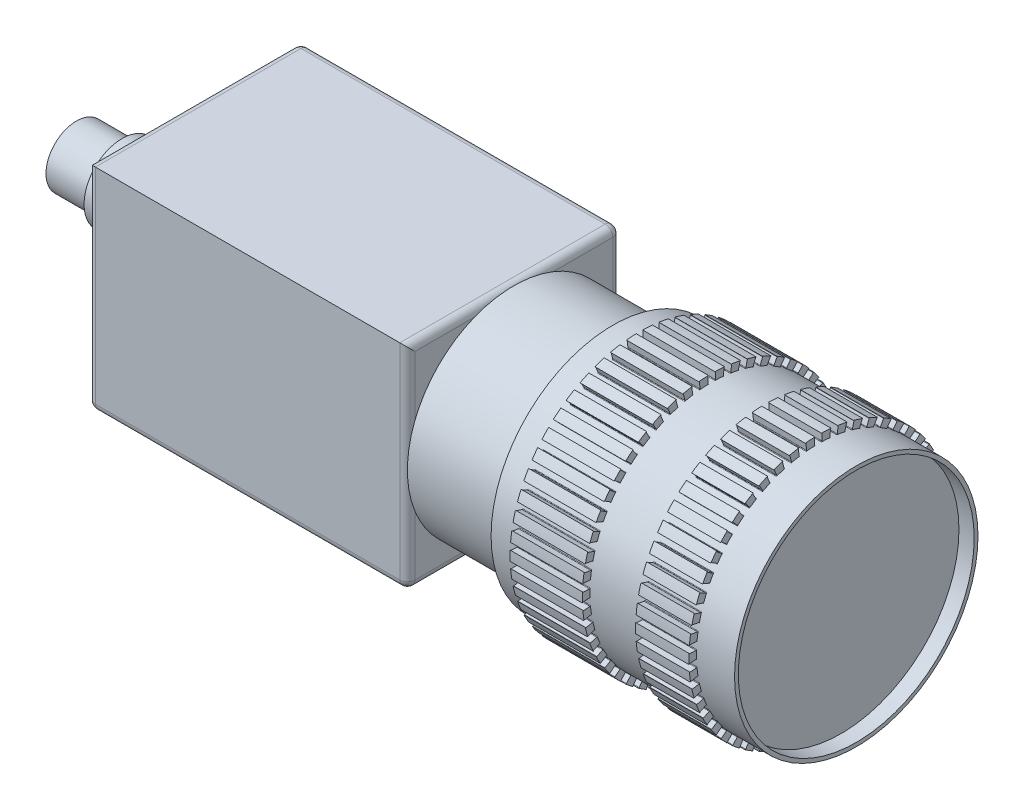
SolidWorks part; units mm, degrees
ref_plane "Front Plane" through (0, 0, 0) normal (0, 0, 1) x (1, 0, 0)
ref_plane "Top Plane" through (0, 0, 0) normal (0, 1, 0) x (1, 0, 0)
ref_plane "Right Plane" through (0, 0, 0) normal (1, 0, 0) x (0, 0, -1)
sketch "Sketch1" plane through (0, 0, 0) normal (0, 1, 0) x (1, 0, 0)
  line L1 (21, -14) -> (-21, -14)
  line L2 (21, -14) -> (21, 14)
  line L3 (21, 14) -> (-21, 14)
  line L4 (-21, -14) -> (-21, 14)
  line L5 (21, -14) -> (-21, 14) construction
  line L6 (21, 14) -> (-21, -14) construction
  point P0 (0, 0)
  dimension "D1" = 42
  dimension "D2" = 28
extrude "Boss-Extrude1" add sketch "Sketch1" along normal blind 28
fillet "Fillet1" radius 1 11 edges at (21, 14, 14) (21, 28, 0) (-21, 28, 0) (-21, 14, 14) (0, 0, 14) (21, 0, 0) (-21, 0, 0) (21, 14, -14) (0, 28, -14) (-21, 14, -14) (0, 0, -14)
sketch "Sketch2" plane through (21, 0, 0) normal (1, 0, 0) x (0, 0, -1)
  circle A0 centre (0, 14) radius 14
  dimension "D1" = 28
  dimension "D2" = 14
extrude "Boss-Extrude2" add sketch "Sketch2" along normal blind 13
sketch "Sketch3" plane through (34, 0, 0) normal (1, 0, 0) x (0, 0, -1)
  circle A0 centre (0, 14) radius 16
  circle A1 centre (0, 14) radius 14 construction
  dimension "D1" = 32
extrude "Boss-Extrude3" add sketch "Sketch3" along normal blind 3.5
sketch "Sketch4" plane through (37.5, 0, 0) normal (1, 0, 0) x (0, 0, -1)
  circle A0 centre (0, 14) radius 17
  circle A1 centre (0, 14) radius 16 construction
  dimension "D1" = 34
extrude "Boss-Extrude4" add sketch "Sketch4" along normal blind 9.5
sketch "Sketch5" plane through (47, 0, 0) normal (1, 0, 0) x (0, 0, -1)
  line L0 (-0.5, 30.9197) -> (-0.5, 30.0694)
  line L1 (1.6245, 30.8489) -> (1.518, 30.0053)
  line L2 (0.5, 30.0694) -> (0.5, 30.9197)
  line L3 (2.5101, 29.88) -> (2.6167, 30.7236)
  line L4 (3.7235, 30.5124) -> (3.512, 29.6889)
  line L5 (4.4806, 29.4402) -> (4.692, 30.2638)
  line L6 (5.7637, 29.9156) -> (5.4506, 29.125)
  line L7 (6.3804, 28.7569) -> (6.6934, 29.5474)
  line L8 (7.713, 29.0677) -> (7.3033, 28.3226)
  line L9 (8.1796, 27.8408) -> (8.5893, 28.5859)
  line L10 (9.5406, 27.9822) -> (9.0408, 27.2943)
  line L11 (9.8499, 26.7065) -> (10.3496, 27.3944)
  line L12 (11.2178, 26.6762) -> (10.6358, 26.0563)
  line L13 (11.3647, 25.3718) -> (11.9468, 25.9916)
  line L14 (12.7181, 25.1703) -> (12.063, 24.6283)
  line L15 (12.7004, 23.8578) -> (13.3555, 24.3997)
  line L16 (14.0178, 23.4882) -> (13.2999, 23.0326)
  line L17 (13.8357, 22.1882) -> (14.5537, 22.6438)
  line L18 (15.0965, 21.6565) -> (14.3271, 21.2944)
  line L19 (14.7529, 20.3896) -> (15.5223, 20.7516)
  line L20 (15.937, 19.704) -> (15.1284, 19.4412)
  line L21 (15.4374, 18.4902) -> (16.2461, 18.7529)
  line L22 (16.5263, 17.6616) -> (15.6911, 17.5022)
  line L23 (15.8784, 16.52) -> (16.7137, 16.6793)
  line L24 (16.8549, 15.5614) -> (16.0063, 15.508)
  line L25 (16.0691, 14.51) -> (16.9177, 14.5634)
  line L26 (16.9177, 13.4366) -> (16.0691, 13.49)
  line L27 (16.0063, 12.492) -> (16.8549, 12.4386)
  line L28 (16.7137, 11.3207) -> (15.8784, 11.48)
  line L29 (15.6911, 10.4978) -> (16.5263, 10.3384)
  line L30 (16.2461, 9.2471) -> (15.4374, 9.5098)
  line L31 (15.1284, 8.5588) -> (15.937, 8.296)
  line L32 (15.5223, 7.2484) -> (14.7529, 7.6104)
  line L33 (14.3271, 6.7056) -> (15.0965, 6.3435)
  line L34 (14.5537, 5.3562) -> (13.8357, 5.8118)
  line L35 (13.2999, 4.9674) -> (14.0178, 4.5118)
  line L36 (13.3555, 3.6003) -> (12.7004, 4.1422)
  line L37 (12.063, 3.3717) -> (12.7181, 2.8297)
  line L38 (11.9468, 2.0084) -> (11.3647, 2.6282)
  line L39 (10.6358, 1.9437) -> (11.2178, 1.3238)
  line L40 (10.3496, 0.6056) -> (9.8499, 1.2935)
  line L41 (9.0408, 0.7057) -> (9.5406, 0.0178)
  line L42 (8.5893, -0.5859) -> (8.1796, 0.1592)
  line L43 (7.3033, -0.3226) -> (7.713, -1.0677)
  line L44 (6.6934, -1.5474) -> (6.3804, -0.7569)
  line L45 (5.4506, -1.125) -> (5.7637, -1.9156)
  line L46 (4.692, -2.2638) -> (4.4806, -1.4402)
  line L47 (3.512, -1.6889) -> (3.7235, -2.5124)
  line L48 (2.6167, -2.7236) -> (2.5101, -1.88)
  line L49 (1.518, -2.0053) -> (1.6245, -2.8489)
  line L50 (0.5, -2.9197) -> (0.5, -2.0694)
  line L51 (-0.5, -2.0694) -> (-0.5, -2.9197)
  line L52 (-1.6245, -2.8489) -> (-1.518, -2.0053)
  line L53 (-2.5101, -1.88) -> (-2.6167, -2.7236)
  line L54 (-3.7235, -2.5124) -> (-3.512, -1.6889)
  line L55 (-4.4806, -1.4402) -> (-4.692, -2.2638)
  line L56 (-5.7637, -1.9156) -> (-5.4506, -1.125)
  line L57 (-6.3804, -0.7569) -> (-6.6934, -1.5474)
  line L58 (-7.713, -1.0677) -> (-7.3033, -0.3226)
  line L59 (-8.1796, 0.1592) -> (-8.5893, -0.5859)
  line L60 (-9.5406, 0.0178) -> (-9.0408, 0.7057)
  line L61 (-9.8499, 1.2935) -> (-10.3496, 0.6056)
  line L62 (-11.2178, 1.3238) -> (-10.6358, 1.9437)
  line L63 (-11.3647, 2.6282) -> (-11.9468, 2.0084)
  line L64 (-12.7181, 2.8297) -> (-12.063, 3.3717)
  line L65 (-12.7004, 4.1422) -> (-13.3555, 3.6003)
  line L66 (-14.0178, 4.5118) -> (-13.2999, 4.9674)
  line L67 (-13.8357, 5.8118) -> (-14.5537, 5.3562)
  line L68 (-15.0965, 6.3435) -> (-14.3271, 6.7056)
  line L69 (-14.7529, 7.6104) -> (-15.5223, 7.2484)
  line L70 (-15.937, 8.296) -> (-15.1284, 8.5588)
  line L71 (-15.4374, 9.5098) -> (-16.2461, 9.2471)
  line L72 (-16.5263, 10.3384) -> (-15.6911, 10.4978)
  line L73 (-15.8784, 11.48) -> (-16.7137, 11.3207)
  line L74 (-16.8549, 12.4386) -> (-16.0063, 12.492)
  line L75 (-16.0691, 13.49) -> (-16.9177, 13.4366)
  line L76 (-16.9177, 14.5634) -> (-16.0691, 14.51)
  line L77 (-16.0063, 15.508) -> (-16.8549, 15.5614)
  line L78 (-16.7137, 16.6793) -> (-15.8784, 16.52)
  line L79 (-15.6911, 17.5022) -> (-16.5263, 17.6616)
  line L80 (-16.2461, 18.7529) -> (-15.4374, 18.4902)
  line L81 (-15.1284, 19.4412) -> (-15.937, 19.704)
  line L82 (-15.5223, 20.7516) -> (-14.7529, 20.3896)
  line L83 (-14.3271, 21.2944) -> (-15.0965, 21.6565)
  line L84 (-14.5537, 22.6438) -> (-13.8357, 22.1882)
  line L85 (-13.2999, 23.0326) -> (-14.0178, 23.4882)
  line L86 (-13.3555, 24.3997) -> (-12.7004, 23.8578)
  line L87 (-12.063, 24.6283) -> (-12.7181, 25.1703)
  line L88 (-11.9468, 25.9916) -> (-11.3647, 25.3718)
  line L89 (-10.6358, 26.0563) -> (-11.2178, 26.6762)
  line L90 (-10.3496, 27.3944) -> (-9.8499, 26.7065)
  line L91 (-9.0408, 27.2943) -> (-9.5406, 27.9822)
  line L92 (-8.5893, 28.5859) -> (-8.1796, 27.8408)
  line L93 (-7.3033, 28.3226) -> (-7.713, 29.0677)
  line L94 (-6.6934, 29.5474) -> (-6.3804, 28.7569)
  line L95 (-5.4506, 29.125) -> (-5.7637, 29.9156)
  line L96 (-4.692, 30.2638) -> (-4.4806, 29.4402)
  line L97 (-3.512, 29.6889) -> (-3.7235, 30.5124)
  line L98 (-2.6167, 30.7236) -> (-2.5101, 29.88)
  line L99 (-1.518, 30.0053) -> (-1.6245, 30.8489)
  arc A0 (0.4269, 30.9946) -> (-0.4269, 30.9946) centre (0, 14) ccw
  arc A1 (0.423, 29.9944) -> (-0.423, 29.9944) centre (0, 14) ccw
  circle A2 centre (0, 14) radius 17 construction
  arc A3 (-0.4269, 30.9946) -> (-0.5, 30.9197) centre (-0.425, 30.9197) ccw
  arc A4 (0.5, 30.9197) -> (0.4269, 30.9946) centre (0.425, 30.9197) ccw
  arc A5 (0.423, 29.9944) -> (0.5, 30.0694) centre (0.425, 30.0694) ccw
  arc A6 (-0.5, 30.0694) -> (-0.423, 29.9944) centre (-0.425, 30.0694) ccw
  arc A7 (1.7065, 30.9141) -> (1.6245, 30.8489) centre (1.6989, 30.8395) ccw
  arc A8 (1.518, 30.0053) -> (1.5849, 29.9213) centre (1.5924, 29.9959) ccw
  arc A9 (2.4243, 29.8153) -> (1.5849, 29.9213) centre (0, 14) ccw
  arc A10 (2.4243, 29.8153) -> (2.5101, 29.88) centre (2.4357, 29.8894) ccw
  arc A11 (2.6167, 30.7236) -> (2.5535, 30.8071) centre (2.5422, 30.733) ccw
  arc A12 (2.5535, 30.8071) -> (1.7065, 30.9141) centre (0, 14) ccw
  arc A13 (3.8129, 30.5669) -> (3.7235, 30.5124) centre (3.7961, 30.4938) ccw
  arc A14 (3.512, 29.6889) -> (3.5679, 29.5971) centre (3.5846, 29.6702) ccw
  arc A15 (4.3874, 29.3867) -> (3.5679, 29.5971) centre (0, 14) ccw
  arc A16 (4.3874, 29.3867) -> (4.4806, 29.4402) centre (4.4079, 29.4588) ccw
  arc A17 (4.692, 30.2638) -> (4.6399, 30.3546) centre (4.6194, 30.2824) ccw
  arc A18 (4.6399, 30.3546) -> (3.8129, 30.5669) centre (0, 14) ccw
  arc A19 (5.8592, 29.9584) -> (5.7637, 29.9156) centre (5.8334, 29.888) ccw
  arc A20 (5.4506, 29.125) -> (5.4946, 29.0269) centre (5.5204, 29.0974) ccw
  arc A21 (6.2812, 28.7155) -> (5.4946, 29.0269) centre (0, 14) ccw
  arc A22 (6.2812, 28.7155) -> (6.3804, 28.7569) centre (6.3107, 28.7845) ccw
  arc A23 (6.6934, 29.5474) -> (6.6531, 29.6441) centre (6.6237, 29.5751) ccw
  arc A24 (6.6531, 29.6441) -> (5.8592, 29.9584) centre (0, 14) ccw
  arc A25 (7.8131, 29.0982) -> (7.713, 29.0677) centre (7.7787, 29.0316) ccw
  arc A26 (7.3033, 28.3226) -> (7.3347, 28.2198) centre (7.3691, 28.2865) ccw
  arc A27 (8.0761, 27.8122) -> (7.3347, 28.2198) centre (0, 14) ccw
  arc A28 (8.0761, 27.8122) -> (8.1796, 27.8408) centre (8.1139, 27.877) ccw
  arc A29 (8.5893, 28.5859) -> (8.5613, 28.6869) centre (8.5235, 28.6221) ccw
  arc A30 (8.5613, 28.6869) -> (7.8131, 29.0982) centre (0, 14) ccw
  arc A31 (9.6438, 27.9999) -> (9.5406, 27.9822) centre (9.6013, 27.9381) ccw
  arc A32 (9.0408, 27.2943) -> (9.059, 27.1884) centre (9.1015, 27.2502) ccw
  arc A33 (9.7435, 26.6911) -> (9.059, 27.1884) centre (0, 14) ccw
  arc A34 (9.7435, 26.6911) -> (9.8499, 26.7065) centre (9.7892, 26.7506) ccw
  arc A35 (10.3496, 27.3944) -> (10.3346, 27.498) centre (10.289, 27.4385) ccw
  arc A36 (10.3346, 27.498) -> (9.6438, 27.9999) centre (0, 14) ccw
  arc A37 (11.3224, 26.6808) -> (11.2178, 26.6762) centre (11.2725, 26.6248) ccw
  arc A38 (10.6358, 26.0563) -> (10.6406, 25.949) centre (10.6904, 26.005) ccw
  arc A39 (11.2573, 25.3698) -> (10.6406, 25.949) centre (0, 14) ccw
  arc A40 (11.2573, 25.3698) -> (11.3647, 25.3718) centre (11.3101, 25.4231) ccw
  arc A41 (11.9468, 25.9916) -> (11.9448, 26.0963) centre (11.8921, 26.043) ccw
  arc A42 (11.9448, 26.0963) -> (11.3224, 26.6808) centre (0, 14) ccw
  arc A43 (12.8225, 25.1617) -> (12.7181, 25.1703) centre (12.7659, 25.1125) ccw
  arc A44 (12.063, 24.6283) -> (12.0543, 24.5212) centre (12.1108, 24.5705) ccw
  arc A45 (12.5935, 23.8693) -> (12.0543, 24.5212) centre (0, 14) ccw
  arc A46 (12.5935, 23.8693) -> (12.7004, 23.8578) centre (12.6526, 23.9155) ccw
  arc A47 (13.3555, 24.3997) -> (13.3667, 24.5039) centre (13.3077, 24.4575) ccw
  arc A48 (13.3667, 24.5039) -> (12.8225, 25.1617) centre (0, 14) ccw
  arc A49 (14.1203, 23.4666) -> (14.0178, 23.4882) centre (14.058, 23.4248) ccw
  arc A50 (13.2999, 23.0326) -> (13.2779, 22.9274) centre (13.3401, 22.9692) ccw
  arc A51 (13.7312, 22.2131) -> (13.2779, 22.9274) centre (0, 14) ccw
  arc A52 (13.7312, 22.2131) -> (13.8357, 22.1882) centre (13.7956, 22.2516) ccw
  arc A53 (14.5537, 22.6438) -> (14.5778, 22.7458) centre (14.5135, 22.7072) ccw
  arc A54 (14.5778, 22.7458) -> (14.1203, 23.4666) centre (0, 14) ccw
  arc A55 (15.1955, 21.6222) -> (15.0965, 21.6565) centre (15.1284, 21.5886) ccw
  arc A56 (14.3271, 21.2944) -> (14.2921, 21.1928) centre (14.3591, 21.2266) ccw
  arc A57 (14.6523, 20.4273) -> (14.2921, 21.1928) centre (0, 14) ccw
  arc A58 (14.6523, 20.4273) -> (14.7529, 20.3896) centre (14.721, 20.4575) ccw
  arc A59 (15.5223, 20.7516) -> (15.559, 20.8497) centre (15.4903, 20.8195) ccw
  arc A60 (15.559, 20.8497) -> (15.1955, 21.6222) centre (0, 14) ccw
  arc A61 (16.0309, 19.6576) -> (15.937, 19.704) centre (15.9602, 19.6327) ccw
  arc A62 (15.1284, 19.4412) -> (15.0809, 19.3449) centre (15.1516, 19.3699) ccw
  arc A63 (15.3423, 18.5402) -> (15.0809, 19.3449) centre (0, 14) ccw
  arc A64 (15.3423, 18.5402) -> (15.4374, 18.4902) centre (15.4142, 18.5615) ccw
  arc A65 (16.2461, 18.7529) -> (16.2948, 18.8456) centre (16.2229, 18.8243) ccw
  arc A66 (16.2948, 18.8456) -> (16.0309, 19.6576) centre (0, 14) ccw
  arc A67 (16.6136, 17.6038) -> (16.5263, 17.6616) centre (16.5403, 17.5879) ccw
  arc A68 (15.6911, 17.5022) -> (15.6318, 17.4126) centre (15.7051, 17.4286) ccw
  arc A69 (15.7904, 16.5815) -> (15.6318, 17.4126) centre (0, 14) ccw
  arc A70 (15.7904, 16.5815) -> (15.8784, 16.52) centre (15.8644, 16.5936) ccw
  arc A71 (16.7137, 16.6793) -> (16.7736, 16.7652) centre (16.6996, 16.753) ccw
  arc A72 (16.7736, 16.7652) -> (16.6136, 17.6038) centre (0, 14) ccw
  arc A73 (16.9343, 15.4931) -> (16.8549, 15.5614) centre (16.8596, 15.4866) ccw
  arc A74 (16.0063, 15.508) -> (15.9363, 15.4265) centre (16.011, 15.4332) ccw
  arc A75 (15.9894, 14.5821) -> (15.9363, 15.4265) centre (0, 14) ccw
  arc A76 (15.9894, 14.5821) -> (16.0691, 14.51) centre (16.0644, 14.5848) ccw
  arc A77 (16.9177, 14.5634) -> (16.9879, 14.6411) centre (16.913, 14.6382) ccw
  arc A78 (16.9879, 14.6411) -> (16.9343, 15.4931) centre (0, 14) ccw
  arc A79 (16.9879, 13.3589) -> (16.9177, 13.4366) centre (16.913, 13.3618) ccw
  arc A80 (16.0691, 13.49) -> (15.9894, 13.4179) centre (16.0644, 13.4152) ccw
  arc A81 (15.9363, 12.5735) -> (15.9894, 13.4179) centre (0, 14) ccw
  arc A82 (15.9363, 12.5735) -> (16.0063, 12.492) centre (16.011, 12.5668) ccw
  arc A83 (16.8549, 12.4386) -> (16.9343, 12.5069) centre (16.8596, 12.5134) ccw
  arc A84 (16.9343, 12.5069) -> (16.9879, 13.3589) centre (0, 14) ccw
  arc A85 (16.7736, 11.2348) -> (16.7137, 11.3207) centre (16.6996, 11.247) ccw
  arc A86 (15.8784, 11.48) -> (15.7904, 11.4185) centre (15.8644, 11.4064) ccw
  arc A87 (15.6318, 10.5874) -> (15.7904, 11.4185) centre (0, 14) ccw
  arc A88 (15.6318, 10.5874) -> (15.6911, 10.4978) centre (15.7051, 10.5714) ccw
  arc A89 (16.5263, 10.3384) -> (16.6136, 10.3962) centre (16.5403, 10.4121) ccw
  arc A90 (16.6136, 10.3962) -> (16.7736, 11.2348) centre (0, 14) ccw
  arc A91 (16.2948, 9.1544) -> (16.2461, 9.2471) centre (16.2229, 9.1757) ccw
  arc A92 (15.4374, 9.5098) -> (15.3423, 9.4598) centre (15.4142, 9.4385) ccw
  arc A93 (15.0809, 8.6551) -> (15.3423, 9.4598) centre (0, 14) ccw
  arc A94 (15.0809, 8.6551) -> (15.1284, 8.5588) centre (15.1516, 8.6301) ccw
  arc A95 (15.937, 8.296) -> (16.0309, 8.3424) centre (15.9602, 8.3673) ccw
  arc A96 (16.0309, 8.3424) -> (16.2948, 9.1544) centre (0, 14) ccw
  arc A97 (15.559, 7.1503) -> (15.5223, 7.2484) centre (15.4903, 7.1805) ccw
  arc A98 (14.7529, 7.6104) -> (14.6523, 7.5727) centre (14.721, 7.5425) ccw
  arc A99 (14.2921, 6.8072) -> (14.6523, 7.5727) centre (0, 14) ccw
  arc A100 (14.2921, 6.8072) -> (14.3271, 6.7056) centre (14.3591, 6.7734) ccw
  arc A101 (15.0965, 6.3435) -> (15.1955, 6.3778) centre (15.1284, 6.4114) ccw
  arc A102 (15.1955, 6.3778) -> (15.559, 7.1503) centre (0, 14) ccw
  arc A103 (14.5778, 5.2542) -> (14.5537, 5.3562) centre (14.5135, 5.2928) ccw
  arc A104 (13.8357, 5.8118) -> (13.7312, 5.7869) centre (13.7956, 5.7484) ccw
  arc A105 (13.2779, 5.0726) -> (13.7312, 5.7869) centre (0, 14) ccw
  arc A106 (13.2779, 5.0726) -> (13.2999, 4.9674) centre (13.3401, 5.0308) ccw
  arc A107 (14.0178, 4.5118) -> (14.1203, 4.5334) centre (14.058, 4.5752) ccw
  arc A108 (14.1203, 4.5334) -> (14.5778, 5.2542) centre (0, 14) ccw
  arc A109 (13.3667, 3.4961) -> (13.3555, 3.6003) centre (13.3077, 3.5425) ccw
  arc A110 (12.7004, 4.1422) -> (12.5935, 4.1307) centre (12.6526, 4.0845) ccw
  arc A111 (12.0543, 3.4788) -> (12.5935, 4.1307) centre (0, 14) ccw
  arc A112 (12.0543, 3.4788) -> (12.063, 3.3717) centre (12.1108, 3.4295) ccw
  arc A113 (12.7181, 2.8297) -> (12.8225, 2.8383) centre (12.7659, 2.8875) ccw
  arc A114 (12.8225, 2.8383) -> (13.3667, 3.4961) centre (0, 14) ccw
  arc A115 (11.9448, 1.9037) -> (11.9468, 2.0084) centre (11.8921, 1.957) ccw
  arc A116 (11.3647, 2.6282) -> (11.2573, 2.6302) centre (11.3101, 2.5769) ccw
  arc A117 (10.6406, 2.051) -> (11.2573, 2.6302) centre (0, 14) ccw
  arc A118 (10.6406, 2.051) -> (10.6358, 1.9437) centre (10.6904, 1.995) ccw
  arc A119 (11.2178, 1.3238) -> (11.3224, 1.3192) centre (11.2725, 1.3752) ccw
  arc A120 (11.3224, 1.3192) -> (11.9448, 1.9037) centre (0, 14) ccw
  arc A121 (10.3346, 0.502) -> (10.3496, 0.6056) centre (10.289, 0.5615) ccw
  arc A122 (9.8499, 1.2935) -> (9.7435, 1.3089) centre (9.7892, 1.2494) ccw
  arc A123 (9.059, 0.8116) -> (9.7435, 1.3089) centre (0, 14) ccw
  arc A124 (9.059, 0.8116) -> (9.0408, 0.7057) centre (9.1015, 0.7498) ccw
  arc A125 (9.5406, 0.0178) -> (9.6438, 0.0001) centre (9.6013, 0.0619) ccw
  arc A126 (9.6438, 0.0001) -> (10.3346, 0.502) centre (0, 14) ccw
  arc A127 (8.5613, -0.6869) -> (8.5893, -0.5859) centre (8.5235, -0.6221) ccw
  arc A128 (8.1796, 0.1592) -> (8.0761, 0.1878) centre (8.1139, 0.123) ccw
  arc A129 (7.3347, -0.2198) -> (8.0761, 0.1878) centre (0, 14) ccw
  arc A130 (7.3347, -0.2198) -> (7.3033, -0.3226) centre (7.3691, -0.2865) ccw
  arc A131 (7.713, -1.0677) -> (7.8131, -1.0982) centre (7.7787, -1.0316) ccw
  arc A132 (7.8131, -1.0982) -> (8.5613, -0.6869) centre (0, 14) ccw
  arc A133 (6.6531, -1.6441) -> (6.6934, -1.5474) centre (6.6237, -1.5751) ccw
  arc A134 (6.3804, -0.7569) -> (6.2812, -0.7155) centre (6.3107, -0.7845) ccw
  arc A135 (5.4946, -1.0269) -> (6.2812, -0.7155) centre (0, 14) ccw
  arc A136 (5.4946, -1.0269) -> (5.4506, -1.125) centre (5.5204, -1.0974) ccw
  arc A137 (5.7637, -1.9156) -> (5.8592, -1.9584) centre (5.8334, -1.888) ccw
  arc A138 (5.8592, -1.9584) -> (6.6531, -1.6441) centre (0, 14) ccw
  arc A139 (4.6399, -2.3546) -> (4.692, -2.2638) centre (4.6194, -2.2824) ccw
  arc A140 (4.4806, -1.4402) -> (4.3874, -1.3867) centre (4.4079, -1.4588) ccw
  arc A141 (3.5679, -1.5971) -> (4.3874, -1.3867) centre (0, 14) ccw
  arc A142 (3.5679, -1.5971) -> (3.512, -1.6889) centre (3.5846, -1.6702) ccw
  arc A143 (3.7235, -2.5124) -> (3.8129, -2.5669) centre (3.7961, -2.4938) ccw
  arc A144 (3.8129, -2.5669) -> (4.6399, -2.3546) centre (0, 14) ccw
  arc A145 (2.5535, -2.8071) -> (2.6167, -2.7236) centre (2.5422, -2.733) ccw
  arc A146 (2.5101, -1.88) -> (2.4243, -1.8153) centre (2.4357, -1.8894) ccw
  arc A147 (1.5849, -1.9213) -> (2.4243, -1.8153) centre (0, 14) ccw
  arc A148 (1.5849, -1.9213) -> (1.518, -2.0053) centre (1.5924, -1.9959) ccw
  arc A149 (1.6245, -2.8489) -> (1.7065, -2.9141) centre (1.6989, -2.8395) ccw
  arc A150 (1.7065, -2.9141) -> (2.5535, -2.8071) centre (0, 14) ccw
  arc A151 (0.4269, -2.9946) -> (0.5, -2.9197) centre (0.425, -2.9197) ccw
  arc A152 (0.5, -2.0694) -> (0.423, -1.9944) centre (0.425, -2.0694) ccw
  arc A153 (-0.423, -1.9944) -> (0.423, -1.9944) centre (0, 14) ccw
  arc A154 (-0.423, -1.9944) -> (-0.5, -2.0694) centre (-0.425, -2.0694) ccw
  arc A155 (-0.5, -2.9197) -> (-0.4269, -2.9946) centre (-0.425, -2.9197) ccw
  arc A156 (-0.4269, -2.9946) -> (0.4269, -2.9946) centre (0, 14) ccw
  arc A157 (-1.7065, -2.9141) -> (-1.6245, -2.8489) centre (-1.6989, -2.8395) ccw
  arc A158 (-1.518, -2.0053) -> (-1.5849, -1.9213) centre (-1.5924, -1.9959) ccw
  arc A159 (-2.4243, -1.8153) -> (-1.5849, -1.9213) centre (0, 14) ccw
  arc A160 (-2.4243, -1.8153) -> (-2.5101, -1.88) centre (-2.4357, -1.8894) ccw
  arc A161 (-2.6167, -2.7236) -> (-2.5535, -2.8071) centre (-2.5422, -2.733) ccw
  arc A162 (-2.5535, -2.8071) -> (-1.7065, -2.9141) centre (0, 14) ccw
  arc A163 (-3.8129, -2.5669) -> (-3.7235, -2.5124) centre (-3.7961, -2.4938) ccw
  arc A164 (-3.512, -1.6889) -> (-3.5679, -1.5971) centre (-3.5846, -1.6702) ccw
  arc A165 (-4.3874, -1.3867) -> (-3.5679, -1.5971) centre (0, 14) ccw
  arc A166 (-4.3874, -1.3867) -> (-4.4806, -1.4402) centre (-4.4079, -1.4588) ccw
  arc A167 (-4.692, -2.2638) -> (-4.6399, -2.3546) centre (-4.6194, -2.2824) ccw
  arc A168 (-4.6399, -2.3546) -> (-3.8129, -2.5669) centre (0, 14) ccw
  arc A169 (-5.8592, -1.9584) -> (-5.7637, -1.9156) centre (-5.8334, -1.888) ccw
  arc A170 (-5.4506, -1.125) -> (-5.4946, -1.0269) centre (-5.5204, -1.0974) ccw
  arc A171 (-6.2812, -0.7155) -> (-5.4946, -1.0269) centre (0, 14) ccw
  arc A172 (-6.2812, -0.7155) -> (-6.3804, -0.7569) centre (-6.3107, -0.7845) ccw
  arc A173 (-6.6934, -1.5474) -> (-6.6531, -1.6441) centre (-6.6237, -1.5751) ccw
  arc A174 (-6.6531, -1.6441) -> (-5.8592, -1.9584) centre (0, 14) ccw
  arc A175 (-7.8131, -1.0982) -> (-7.713, -1.0677) centre (-7.7787, -1.0316) ccw
  arc A176 (-7.3033, -0.3226) -> (-7.3347, -0.2198) centre (-7.3691, -0.2865) ccw
  arc A177 (-8.0761, 0.1878) -> (-7.3347, -0.2198) centre (0, 14) ccw
  arc A178 (-8.0761, 0.1878) -> (-8.1796, 0.1592) centre (-8.1139, 0.123) ccw
  arc A179 (-8.5893, -0.5859) -> (-8.5613, -0.6869) centre (-8.5235, -0.6221) ccw
  arc A180 (-8.5613, -0.6869) -> (-7.8131, -1.0982) centre (0, 14) ccw
  arc A181 (-9.6438, 0.0001) -> (-9.5406, 0.0178) centre (-9.6013, 0.0619) ccw
  arc A182 (-9.0408, 0.7057) -> (-9.059, 0.8116) centre (-9.1015, 0.7498) ccw
  arc A183 (-9.7435, 1.3089) -> (-9.059, 0.8116) centre (0, 14) ccw
  arc A184 (-9.7435, 1.3089) -> (-9.8499, 1.2935) centre (-9.7892, 1.2494) ccw
  arc A185 (-10.3496, 0.6056) -> (-10.3346, 0.502) centre (-10.289, 0.5615) ccw
  arc A186 (-10.3346, 0.502) -> (-9.6438, 0.0001) centre (0, 14) ccw
  arc A187 (-11.3224, 1.3192) -> (-11.2178, 1.3238) centre (-11.2725, 1.3752) ccw
  arc A188 (-10.6358, 1.9437) -> (-10.6406, 2.051) centre (-10.6904, 1.995) ccw
  arc A189 (-11.2573, 2.6302) -> (-10.6406, 2.051) centre (0, 14) ccw
  arc A190 (-11.2573, 2.6302) -> (-11.3647, 2.6282) centre (-11.3101, 2.5769) ccw
  arc A191 (-11.9468, 2.0084) -> (-11.9448, 1.9037) centre (-11.8921, 1.957) ccw
  arc A192 (-11.9448, 1.9037) -> (-11.3224, 1.3192) centre (0, 14) ccw
  arc A193 (-12.8225, 2.8383) -> (-12.7181, 2.8297) centre (-12.7659, 2.8875) ccw
  arc A194 (-12.063, 3.3717) -> (-12.0543, 3.4788) centre (-12.1108, 3.4295) ccw
  arc A195 (-12.5935, 4.1307) -> (-12.0543, 3.4788) centre (0, 14) ccw
  arc A196 (-12.5935, 4.1307) -> (-12.7004, 4.1422) centre (-12.6526, 4.0845) ccw
  arc A197 (-13.3555, 3.6003) -> (-13.3667, 3.4961) centre (-13.3077, 3.5425) ccw
  arc A198 (-13.3667, 3.4961) -> (-12.8225, 2.8383) centre (0, 14) ccw
  arc A199 (-14.1203, 4.5334) -> (-14.0178, 4.5118) centre (-14.058, 4.5752) ccw
  arc A200 (-13.2999, 4.9674) -> (-13.2779, 5.0726) centre (-13.3401, 5.0308) ccw
  arc A201 (-13.7312, 5.7869) -> (-13.2779, 5.0726) centre (0, 14) ccw
  arc A202 (-13.7312, 5.7869) -> (-13.8357, 5.8118) centre (-13.7956, 5.7484) ccw
  arc A203 (-14.5537, 5.3562) -> (-14.5778, 5.2542) centre (-14.5135, 5.2928) ccw
  arc A204 (-14.5778, 5.2542) -> (-14.1203, 4.5334) centre (0, 14) ccw
  arc A205 (-15.1955, 6.3778) -> (-15.0965, 6.3435) centre (-15.1284, 6.4114) ccw
  arc A206 (-14.3271, 6.7056) -> (-14.2921, 6.8072) centre (-14.3591, 6.7734) ccw
  arc A207 (-14.6523, 7.5727) -> (-14.2921, 6.8072) centre (0, 14) ccw
  arc A208 (-14.6523, 7.5727) -> (-14.7529, 7.6104) centre (-14.721, 7.5425) ccw
  arc A209 (-15.5223, 7.2484) -> (-15.559, 7.1503) centre (-15.4903, 7.1805) ccw
  arc A210 (-15.559, 7.1503) -> (-15.1955, 6.3778) centre (0, 14) ccw
  arc A211 (-16.0309, 8.3424) -> (-15.937, 8.296) centre (-15.9602, 8.3673) ccw
  arc A212 (-15.1284, 8.5588) -> (-15.0809, 8.6551) centre (-15.1516, 8.6301) ccw
  arc A213 (-15.3423, 9.4598) -> (-15.0809, 8.6551) centre (0, 14) ccw
  arc A214 (-15.3423, 9.4598) -> (-15.4374, 9.5098) centre (-15.4142, 9.4385) ccw
  arc A215 (-16.2461, 9.2471) -> (-16.2948, 9.1544) centre (-16.2229, 9.1757) ccw
  arc A216 (-16.2948, 9.1544) -> (-16.0309, 8.3424) centre (0, 14) ccw
  arc A217 (-16.6136, 10.3962) -> (-16.5263, 10.3384) centre (-16.5403, 10.4121) ccw
  arc A218 (-15.6911, 10.4978) -> (-15.6318, 10.5874) centre (-15.7051, 10.5714) ccw
  arc A219 (-15.7904, 11.4185) -> (-15.6318, 10.5874) centre (0, 14) ccw
  arc A220 (-15.7904, 11.4185) -> (-15.8784, 11.48) centre (-15.8644, 11.4064) ccw
  arc A221 (-16.7137, 11.3207) -> (-16.7736, 11.2348) centre (-16.6996, 11.247) ccw
  arc A222 (-16.7736, 11.2348) -> (-16.6136, 10.3962) centre (0, 14) ccw
  arc A223 (-16.9343, 12.5069) -> (-16.8549, 12.4386) centre (-16.8596, 12.5134) ccw
  arc A224 (-16.0063, 12.492) -> (-15.9363, 12.5735) centre (-16.011, 12.5668) ccw
  arc A225 (-15.9894, 13.4179) -> (-15.9363, 12.5735) centre (0, 14) ccw
  arc A226 (-15.9894, 13.4179) -> (-16.0691, 13.49) centre (-16.0644, 13.4152) ccw
  arc A227 (-16.9177, 13.4366) -> (-16.9879, 13.3589) centre (-16.913, 13.3618) ccw
  arc A228 (-16.9879, 13.3589) -> (-16.9343, 12.5069) centre (0, 14) ccw
  arc A229 (-16.9879, 14.6411) -> (-16.9177, 14.5634) centre (-16.913, 14.6382) ccw
  arc A230 (-16.0691, 14.51) -> (-15.9894, 14.5821) centre (-16.0644, 14.5848) ccw
  arc A231 (-15.9363, 15.4265) -> (-15.9894, 14.5821) centre (0, 14) ccw
  arc A232 (-15.9363, 15.4265) -> (-16.0063, 15.508) centre (-16.011, 15.4332) ccw
  arc A233 (-16.8549, 15.5614) -> (-16.9343, 15.4931) centre (-16.8596, 15.4866) ccw
  arc A234 (-16.9343, 15.4931) -> (-16.9879, 14.6411) centre (0, 14) ccw
  arc A235 (-16.7736, 16.7652) -> (-16.7137, 16.6793) centre (-16.6996, 16.753) ccw
  arc A236 (-15.8784, 16.52) -> (-15.7904, 16.5815) centre (-15.8644, 16.5936) ccw
  arc A237 (-15.6318, 17.4126) -> (-15.7904, 16.5815) centre (0, 14) ccw
  arc A238 (-15.6318, 17.4126) -> (-15.6911, 17.5022) centre (-15.7051, 17.4286) ccw
  arc A239 (-16.5263, 17.6616) -> (-16.6136, 17.6038) centre (-16.5403, 17.5879) ccw
  arc A240 (-16.6136, 17.6038) -> (-16.7736, 16.7652) centre (0, 14) ccw
  arc A241 (-16.2948, 18.8456) -> (-16.2461, 18.7529) centre (-16.2229, 18.8243) ccw
  arc A242 (-15.4374, 18.4902) -> (-15.3423, 18.5402) centre (-15.4142, 18.5615) ccw
  arc A243 (-15.0809, 19.3449) -> (-15.3423, 18.5402) centre (0, 14) ccw
  arc A244 (-15.0809, 19.3449) -> (-15.1284, 19.4412) centre (-15.1516, 19.3699) ccw
  arc A245 (-15.937, 19.704) -> (-16.0309, 19.6576) centre (-15.9602, 19.6327) ccw
  arc A246 (-16.0309, 19.6576) -> (-16.2948, 18.8456) centre (0, 14) ccw
  arc A247 (-15.559, 20.8497) -> (-15.5223, 20.7516) centre (-15.4903, 20.8195) ccw
  arc A248 (-14.7529, 20.3896) -> (-14.6523, 20.4273) centre (-14.721, 20.4575) ccw
  arc A249 (-14.2921, 21.1928) -> (-14.6523, 20.4273) centre (0, 14) ccw
  arc A250 (-14.2921, 21.1928) -> (-14.3271, 21.2944) centre (-14.3591, 21.2266) ccw
  arc A251 (-15.0965, 21.6565) -> (-15.1955, 21.6222) centre (-15.1284, 21.5886) ccw
  arc A252 (-15.1955, 21.6222) -> (-15.559, 20.8497) centre (0, 14) ccw
  arc A253 (-14.5778, 22.7458) -> (-14.5537, 22.6438) centre (-14.5135, 22.7072) ccw
  arc A254 (-13.8357, 22.1882) -> (-13.7312, 22.2131) centre (-13.7956, 22.2516) ccw
  arc A255 (-13.2779, 22.9274) -> (-13.7312, 22.2131) centre (0, 14) ccw
  arc A256 (-13.2779, 22.9274) -> (-13.2999, 23.0326) centre (-13.3401, 22.9692) ccw
  arc A257 (-14.0178, 23.4882) -> (-14.1203, 23.4666) centre (-14.058, 23.4248) ccw
  arc A258 (-14.1203, 23.4666) -> (-14.5778, 22.7458) centre (0, 14) ccw
  arc A259 (-13.3667, 24.5039) -> (-13.3555, 24.3997) centre (-13.3077, 24.4575) ccw
  arc A260 (-12.7004, 23.8578) -> (-12.5935, 23.8693) centre (-12.6526, 23.9155) ccw
  arc A261 (-12.0543, 24.5212) -> (-12.5935, 23.8693) centre (0, 14) ccw
  arc A262 (-12.0543, 24.5212) -> (-12.063, 24.6283) centre (-12.1108, 24.5705) ccw
  arc A263 (-12.7181, 25.1703) -> (-12.8225, 25.1617) centre (-12.7659, 25.1125) ccw
  arc A264 (-12.8225, 25.1617) -> (-13.3667, 24.5039) centre (0, 14) ccw
  arc A265 (-11.9448, 26.0963) -> (-11.9468, 25.9916) centre (-11.8921, 26.043) ccw
  arc A266 (-11.3647, 25.3718) -> (-11.2573, 25.3698) centre (-11.3101, 25.4231) ccw
  arc A267 (-10.6406, 25.949) -> (-11.2573, 25.3698) centre (0, 14) ccw
  arc A268 (-10.6406, 25.949) -> (-10.6358, 26.0563) centre (-10.6904, 26.005) ccw
  arc A269 (-11.2178, 26.6762) -> (-11.3224, 26.6808) centre (-11.2725, 26.6248) ccw
  arc A270 (-11.3224, 26.6808) -> (-11.9448, 26.0963) centre (0, 14) ccw
  arc A271 (-10.3346, 27.498) -> (-10.3496, 27.3944) centre (-10.289, 27.4385) ccw
  arc A272 (-9.8499, 26.7065) -> (-9.7435, 26.6911) centre (-9.7892, 26.7506) ccw
  arc A273 (-9.059, 27.1884) -> (-9.7435, 26.6911) centre (0, 14) ccw
  arc A274 (-9.059, 27.1884) -> (-9.0408, 27.2943) centre (-9.1015, 27.2502) ccw
  arc A275 (-9.5406, 27.9822) -> (-9.6438, 27.9999) centre (-9.6013, 27.9381) ccw
  arc A276 (-9.6438, 27.9999) -> (-10.3346, 27.498) centre (0, 14) ccw
  arc A277 (-8.5613, 28.6869) -> (-8.5893, 28.5859) centre (-8.5235, 28.6221) ccw
  arc A278 (-8.1796, 27.8408) -> (-8.0761, 27.8122) centre (-8.1139, 27.877) ccw
  arc A279 (-7.3347, 28.2198) -> (-8.0761, 27.8122) centre (0, 14) ccw
  arc A280 (-7.3347, 28.2198) -> (-7.3033, 28.3226) centre (-7.3691, 28.2865) ccw
  arc A281 (-7.713, 29.0677) -> (-7.8131, 29.0982) centre (-7.7787, 29.0316) ccw
  arc A282 (-7.8131, 29.0982) -> (-8.5613, 28.6869) centre (0, 14) ccw
  arc A283 (-6.6531, 29.6441) -> (-6.6934, 29.5474) centre (-6.6237, 29.5751) ccw
  arc A284 (-6.3804, 28.7569) -> (-6.2812, 28.7155) centre (-6.3107, 28.7845) ccw
  arc A285 (-5.4946, 29.0269) -> (-6.2812, 28.7155) centre (0, 14) ccw
  arc A286 (-5.4946, 29.0269) -> (-5.4506, 29.125) centre (-5.5204, 29.0974) ccw
  arc A287 (-5.7637, 29.9156) -> (-5.8592, 29.9584) centre (-5.8334, 29.888) ccw
  arc A288 (-5.8592, 29.9584) -> (-6.6531, 29.6441) centre (0, 14) ccw
  arc A289 (-4.6399, 30.3546) -> (-4.692, 30.2638) centre (-4.6194, 30.2824) ccw
  arc A290 (-4.4806, 29.4402) -> (-4.3874, 29.3867) centre (-4.4079, 29.4588) ccw
  arc A291 (-3.5679, 29.5971) -> (-4.3874, 29.3867) centre (0, 14) ccw
  arc A292 (-3.5679, 29.5971) -> (-3.512, 29.6889) centre (-3.5846, 29.6702) ccw
  arc A293 (-3.7235, 30.5124) -> (-3.8129, 30.5669) centre (-3.7961, 30.4938) ccw
  arc A294 (-3.8129, 30.5669) -> (-4.6399, 30.3546) centre (0, 14) ccw
  arc A295 (-2.5535, 30.8071) -> (-2.6167, 30.7236) centre (-2.5422, 30.733) ccw
  arc A296 (-2.5101, 29.88) -> (-2.4243, 29.8153) centre (-2.4357, 29.8894) ccw
  arc A297 (-1.5849, 29.9213) -> (-2.4243, 29.8153) centre (0, 14) ccw
  arc A298 (-1.5849, 29.9213) -> (-1.518, 30.0053) centre (-1.5924, 29.9959) ccw
  arc A299 (-1.6245, 30.8489) -> (-1.7065, 30.9141) centre (-1.6989, 30.8395) ccw
  arc A300 (-1.7065, 30.9141) -> (-2.5535, 30.8071) centre (0, 14) ccw
  dimension "D1" = 34
  dimension "D2" = 32
  dimension "D5" = 0.15
  dimension "D3" = 1
  dimension "D4" = 0.5
  dimension "D6" = 50
extrude "Cut-Extrude1" cut sketch "Sketch5" against normal blind 9.5
sketch "Sketch6" plane through (47, 0, 0) normal (1, 0, 0) x (0, 0, -1)
  circle A0 centre (0, 14) radius 16
  arc A2 (1.5849, -1.9213) -> (2.4243, -1.8153) centre (0, 14) ccw construction
  dimension "D1" = 32
extrude "Boss-Extrude5" add sketch "Sketch6" along normal blind 7
sketch "Sketch7" plane through (54, 0, 0) normal (1, 0, 0) x (0, 0, -1)
  circle A0 centre (0, 14) radius 17
  arc A2 (16.0309, 19.6576) -> (15.559, 20.8497) centre (0, 14) ccw construction
  dimension "D1" = 34
extrude "Boss-Extrude6" add sketch "Sketch7" along normal blind 7
sketch "Sketch8" plane through (61, 0, 0) normal (1, 0, 0) x (0, 0, -1)
  line L0 (-0.5, 30.9197) -> (-0.5, 30.0694)
  line L1 (1.6245, 30.8489) -> (1.518, 30.0053)
  line L2 (0.5, 30.0694) -> (0.5, 30.9197)
  line L3 (2.5101, 29.88) -> (2.6167, 30.7236)
  line L4 (3.7235, 30.5124) -> (3.512, 29.6889)
  line L5 (4.4806, 29.4402) -> (4.692, 30.2638)
  line L6 (5.7637, 29.9156) -> (5.4506, 29.125)
  line L7 (6.3804, 28.7569) -> (6.6934, 29.5474)
  line L8 (7.713, 29.0677) -> (7.3033, 28.3226)
  line L9 (8.1796, 27.8408) -> (8.5893, 28.5859)
  line L10 (9.5406, 27.9822) -> (9.0408, 27.2943)
  line L11 (9.8499, 26.7065) -> (10.3496, 27.3944)
  line L12 (11.2178, 26.6762) -> (10.6358, 26.0563)
  line L13 (11.3647, 25.3718) -> (11.9468, 25.9916)
  line L14 (12.7181, 25.1703) -> (12.063, 24.6283)
  line L15 (12.7004, 23.8578) -> (13.3555, 24.3997)
  line L16 (14.0178, 23.4882) -> (13.2999, 23.0326)
  line L17 (13.8357, 22.1882) -> (14.5537, 22.6438)
  line L18 (15.0965, 21.6565) -> (14.3271, 21.2944)
  line L19 (14.7529, 20.3896) -> (15.5223, 20.7516)
  line L20 (15.937, 19.704) -> (15.1284, 19.4412)
  line L21 (15.4374, 18.4902) -> (16.2461, 18.7529)
  line L22 (16.5263, 17.6616) -> (15.6911, 17.5022)
  line L23 (15.8784, 16.52) -> (16.7137, 16.6793)
  line L24 (16.8549, 15.5614) -> (16.0063, 15.508)
  line L25 (16.0691, 14.51) -> (16.9177, 14.5634)
  line L26 (16.9177, 13.4366) -> (16.0691, 13.49)
  line L27 (16.0063, 12.492) -> (16.8549, 12.4386)
  line L28 (16.7137, 11.3207) -> (15.8784, 11.48)
  line L29 (15.6911, 10.4978) -> (16.5263, 10.3384)
  line L30 (16.2461, 9.2471) -> (15.4374, 9.5098)
  line L31 (15.1284, 8.5588) -> (15.937, 8.296)
  line L32 (15.5223, 7.2484) -> (14.7529, 7.6104)
  line L33 (14.3271, 6.7056) -> (15.0965, 6.3435)
  line L34 (14.5537, 5.3562) -> (13.8357, 5.8118)
  line L35 (13.2999, 4.9674) -> (14.0178, 4.5118)
  line L36 (13.3555, 3.6003) -> (12.7004, 4.1422)
  line L37 (12.063, 3.3717) -> (12.7181, 2.8297)
  line L38 (11.9468, 2.0084) -> (11.3647, 2.6282)
  line L39 (10.6358, 1.9437) -> (11.2178, 1.3238)
  line L40 (10.3496, 0.6056) -> (9.8499, 1.2935)
  line L41 (9.0408, 0.7057) -> (9.5406, 0.0178)
  line L42 (8.5893, -0.5859) -> (8.1796, 0.1592)
  line L43 (7.3033, -0.3226) -> (7.713, -1.0677)
  line L44 (6.6934, -1.5474) -> (6.3804, -0.7569)
  line L45 (5.4506, -1.125) -> (5.7637, -1.9156)
  line L46 (4.692, -2.2638) -> (4.4806, -1.4402)
  line L47 (3.512, -1.6889) -> (3.7235, -2.5124)
  line L48 (2.6167, -2.7236) -> (2.5101, -1.88)
  line L49 (1.518, -2.0053) -> (1.6245, -2.8489)
  line L50 (0.5, -2.9197) -> (0.5, -2.0694)
  line L51 (-0.5, -2.0694) -> (-0.5, -2.9197)
  line L52 (-1.6245, -2.8489) -> (-1.518, -2.0053)
  line L53 (-2.5101, -1.88) -> (-2.6167, -2.7236)
  line L54 (-3.7235, -2.5124) -> (-3.512, -1.6889)
  line L55 (-4.4806, -1.4402) -> (-4.692, -2.2638)
  line L56 (-5.7637, -1.9156) -> (-5.4506, -1.125)
  line L57 (-6.3804, -0.7569) -> (-6.6934, -1.5474)
  line L58 (-7.713, -1.0677) -> (-7.3033, -0.3226)
  line L59 (-8.1796, 0.1592) -> (-8.5893, -0.5859)
  line L60 (-9.5406, 0.0178) -> (-9.0408, 0.7057)
  line L61 (-9.8499, 1.2935) -> (-10.3496, 0.6056)
  line L62 (-11.2178, 1.3238) -> (-10.6358, 1.9437)
  line L63 (-11.3647, 2.6282) -> (-11.9468, 2.0084)
  line L64 (-12.7181, 2.8297) -> (-12.063, 3.3717)
  line L65 (-12.7004, 4.1422) -> (-13.3555, 3.6003)
  line L66 (-14.0178, 4.5118) -> (-13.2999, 4.9674)
  line L67 (-13.8357, 5.8118) -> (-14.5537, 5.3562)
  line L68 (-15.0965, 6.3435) -> (-14.3271, 6.7056)
  line L69 (-14.7529, 7.6104) -> (-15.5223, 7.2484)
  line L70 (-15.937, 8.296) -> (-15.1284, 8.5588)
  line L71 (-15.4374, 9.5098) -> (-16.2461, 9.2471)
  line L72 (-16.5263, 10.3384) -> (-15.6911, 10.4978)
  line L73 (-15.8784, 11.48) -> (-16.7137, 11.3207)
  line L74 (-16.8549, 12.4386) -> (-16.0063, 12.492)
  line L75 (-16.0691, 13.49) -> (-16.9177, 13.4366)
  line L76 (-16.9177, 14.5634) -> (-16.0691, 14.51)
  line L77 (-16.0063, 15.508) -> (-16.8549, 15.5614)
  line L78 (-16.7137, 16.6793) -> (-15.8784, 16.52)
  line L79 (-15.6911, 17.5022) -> (-16.5263, 17.6616)
  line L80 (-16.2461, 18.7529) -> (-15.4374, 18.4902)
  line L81 (-15.1284, 19.4412) -> (-15.937, 19.704)
  line L82 (-15.5223, 20.7516) -> (-14.7529, 20.3896)
  line L83 (-14.3271, 21.2944) -> (-15.0965, 21.6565)
  line L84 (-14.5537, 22.6438) -> (-13.8357, 22.1882)
  line L85 (-13.2999, 23.0326) -> (-14.0178, 23.4882)
  line L86 (-13.3555, 24.3997) -> (-12.7004, 23.8578)
  line L87 (-12.063, 24.6283) -> (-12.7181, 25.1703)
  line L88 (-11.9468, 25.9916) -> (-11.3647, 25.3718)
  line L89 (-10.6358, 26.0563) -> (-11.2178, 26.6762)
  line L90 (-10.3496, 27.3944) -> (-9.8499, 26.7065)
  line L91 (-9.0408, 27.2943) -> (-9.5406, 27.9822)
  line L92 (-8.5893, 28.5859) -> (-8.1796, 27.8408)
  line L93 (-7.3033, 28.3226) -> (-7.713, 29.0677)
  line L94 (-6.6934, 29.5474) -> (-6.3804, 28.7569)
  line L95 (-5.4506, 29.125) -> (-5.7637, 29.9156)
  line L96 (-4.692, 30.2638) -> (-4.4806, 29.4402)
  line L97 (-3.512, 29.6889) -> (-3.7235, 30.5124)
  line L98 (-2.6167, 30.7236) -> (-2.5101, 29.88)
  line L99 (-1.518, 30.0053) -> (-1.6245, 30.8489)
  arc A0 (0.4269, 30.9946) -> (-0.4269, 30.9946) centre (0, 14) ccw
  arc A1 (0.423, 29.9944) -> (-0.423, 29.9944) centre (0, 14) ccw
  circle A2 centre (0, 14) radius 17 construction
  arc A3 (-0.4269, 30.9946) -> (-0.5, 30.9197) centre (-0.425, 30.9197) ccw
  arc A4 (0.5, 30.9197) -> (0.4269, 30.9946) centre (0.425, 30.9197) ccw
  arc A5 (0.423, 29.9944) -> (0.5, 30.0694) centre (0.425, 30.0694) ccw
  arc A6 (-0.5, 30.0694) -> (-0.423, 29.9944) centre (-0.425, 30.0694) ccw
  arc A7 (1.7065, 30.9141) -> (1.6245, 30.8489) centre (1.6989, 30.8395) ccw
  arc A8 (1.518, 30.0053) -> (1.5849, 29.9213) centre (1.5924, 29.9959) ccw
  arc A9 (2.4243, 29.8153) -> (1.5849, 29.9213) centre (0, 14) ccw
  arc A10 (2.4243, 29.8153) -> (2.5101, 29.88) centre (2.4357, 29.8894) ccw
  arc A11 (2.6167, 30.7236) -> (2.5535, 30.8071) centre (2.5422, 30.733) ccw
  arc A12 (2.5535, 30.8071) -> (1.7065, 30.9141) centre (0, 14) ccw
  arc A13 (3.8129, 30.5669) -> (3.7235, 30.5124) centre (3.7961, 30.4938) ccw
  arc A14 (3.512, 29.6889) -> (3.5679, 29.5971) centre (3.5846, 29.6702) ccw
  arc A15 (4.3874, 29.3867) -> (3.5679, 29.5971) centre (0, 14) ccw
  arc A16 (4.3874, 29.3867) -> (4.4806, 29.4402) centre (4.4079, 29.4588) ccw
  arc A17 (4.692, 30.2638) -> (4.6399, 30.3546) centre (4.6194, 30.2824) ccw
  arc A18 (4.6399, 30.3546) -> (3.8129, 30.5669) centre (0, 14) ccw
  arc A19 (5.8592, 29.9584) -> (5.7637, 29.9156) centre (5.8334, 29.888) ccw
  arc A20 (5.4506, 29.125) -> (5.4946, 29.0269) centre (5.5204, 29.0974) ccw
  arc A21 (6.2812, 28.7155) -> (5.4946, 29.0269) centre (0, 14) ccw
  arc A22 (6.2812, 28.7155) -> (6.3804, 28.7569) centre (6.3107, 28.7845) ccw
  arc A23 (6.6934, 29.5474) -> (6.6531, 29.6441) centre (6.6237, 29.5751) ccw
  arc A24 (6.6531, 29.6441) -> (5.8592, 29.9584) centre (0, 14) ccw
  arc A25 (7.8131, 29.0982) -> (7.713, 29.0677) centre (7.7787, 29.0316) ccw
  arc A26 (7.3033, 28.3226) -> (7.3347, 28.2198) centre (7.3691, 28.2865) ccw
  arc A27 (8.0761, 27.8122) -> (7.3347, 28.2198) centre (0, 14) ccw
  arc A28 (8.0761, 27.8122) -> (8.1796, 27.8408) centre (8.1139, 27.877) ccw
  arc A29 (8.5893, 28.5859) -> (8.5613, 28.6869) centre (8.5235, 28.6221) ccw
  arc A30 (8.5613, 28.6869) -> (7.8131, 29.0982) centre (0, 14) ccw
  arc A31 (9.6438, 27.9999) -> (9.5406, 27.9822) centre (9.6013, 27.9381) ccw
  arc A32 (9.0408, 27.2943) -> (9.059, 27.1884) centre (9.1015, 27.2502) ccw
  arc A33 (9.7435, 26.6911) -> (9.059, 27.1884) centre (0, 14) ccw
  arc A34 (9.7435, 26.6911) -> (9.8499, 26.7065) centre (9.7892, 26.7506) ccw
  arc A35 (10.3496, 27.3944) -> (10.3346, 27.498) centre (10.289, 27.4385) ccw
  arc A36 (10.3346, 27.498) -> (9.6438, 27.9999) centre (0, 14) ccw
  arc A37 (11.3224, 26.6808) -> (11.2178, 26.6762) centre (11.2725, 26.6248) ccw
  arc A38 (10.6358, 26.0563) -> (10.6406, 25.949) centre (10.6904, 26.005) ccw
  arc A39 (11.2573, 25.3698) -> (10.6406, 25.949) centre (0, 14) ccw
  arc A40 (11.2573, 25.3698) -> (11.3647, 25.3718) centre (11.3101, 25.4231) ccw
  arc A41 (11.9468, 25.9916) -> (11.9448, 26.0963) centre (11.8921, 26.043) ccw
  arc A42 (11.9448, 26.0963) -> (11.3224, 26.6808) centre (0, 14) ccw
  arc A43 (12.8225, 25.1617) -> (12.7181, 25.1703) centre (12.7659, 25.1125) ccw
  arc A44 (12.063, 24.6283) -> (12.0543, 24.5212) centre (12.1108, 24.5705) ccw
  arc A45 (12.5935, 23.8693) -> (12.0543, 24.5212) centre (0, 14) ccw
  arc A46 (12.5935, 23.8693) -> (12.7004, 23.8578) centre (12.6526, 23.9155) ccw
  arc A47 (13.3555, 24.3997) -> (13.3667, 24.5039) centre (13.3077, 24.4575) ccw
  arc A48 (13.3667, 24.5039) -> (12.8225, 25.1617) centre (0, 14) ccw
  arc A49 (14.1203, 23.4666) -> (14.0178, 23.4882) centre (14.058, 23.4248) ccw
  arc A50 (13.2999, 23.0326) -> (13.2779, 22.9274) centre (13.3401, 22.9692) ccw
  arc A51 (13.7312, 22.2131) -> (13.2779, 22.9274) centre (0, 14) ccw
  arc A52 (13.7312, 22.2131) -> (13.8357, 22.1882) centre (13.7956, 22.2516) ccw
  arc A53 (14.5537, 22.6438) -> (14.5778, 22.7458) centre (14.5135, 22.7072) ccw
  arc A54 (14.5778, 22.7458) -> (14.1203, 23.4666) centre (0, 14) ccw
  arc A55 (15.1955, 21.6222) -> (15.0965, 21.6565) centre (15.1284, 21.5886) ccw
  arc A56 (14.3271, 21.2944) -> (14.2921, 21.1928) centre (14.3591, 21.2266) ccw
  arc A57 (14.6523, 20.4273) -> (14.2921, 21.1928) centre (0, 14) ccw
  arc A58 (14.6523, 20.4273) -> (14.7529, 20.3896) centre (14.721, 20.4575) ccw
  arc A59 (15.5223, 20.7516) -> (15.559, 20.8497) centre (15.4903, 20.8195) ccw
  arc A60 (15.559, 20.8497) -> (15.1955, 21.6222) centre (0, 14) ccw
  arc A61 (16.0309, 19.6576) -> (15.937, 19.704) centre (15.9602, 19.6327) ccw
  arc A62 (15.1284, 19.4412) -> (15.0809, 19.3449) centre (15.1516, 19.3699) ccw
  arc A63 (15.3423, 18.5402) -> (15.0809, 19.3449) centre (0, 14) ccw
  arc A64 (15.3423, 18.5402) -> (15.4374, 18.4902) centre (15.4142, 18.5615) ccw
  arc A65 (16.2461, 18.7529) -> (16.2948, 18.8456) centre (16.2229, 18.8243) ccw
  arc A66 (16.2948, 18.8456) -> (16.0309, 19.6576) centre (0, 14) ccw
  arc A67 (16.6136, 17.6038) -> (16.5263, 17.6616) centre (16.5403, 17.5879) ccw
  arc A68 (15.6911, 17.5022) -> (15.6318, 17.4126) centre (15.7051, 17.4286) ccw
  arc A69 (15.7904, 16.5815) -> (15.6318, 17.4126) centre (0, 14) ccw
  arc A70 (15.7904, 16.5815) -> (15.8784, 16.52) centre (15.8644, 16.5936) ccw
  arc A71 (16.7137, 16.6793) -> (16.7736, 16.7652) centre (16.6996, 16.753) ccw
  arc A72 (16.7736, 16.7652) -> (16.6136, 17.6038) centre (0, 14) ccw
  arc A73 (16.9343, 15.4931) -> (16.8549, 15.5614) centre (16.8596, 15.4866) ccw
  arc A74 (16.0063, 15.508) -> (15.9363, 15.4265) centre (16.011, 15.4332) ccw
  arc A75 (15.9894, 14.5821) -> (15.9363, 15.4265) centre (0, 14) ccw
  arc A76 (15.9894, 14.5821) -> (16.0691, 14.51) centre (16.0644, 14.5848) ccw
  arc A77 (16.9177, 14.5634) -> (16.9879, 14.6411) centre (16.913, 14.6382) ccw
  arc A78 (16.9879, 14.6411) -> (16.9343, 15.4931) centre (0, 14) ccw
  arc A79 (16.9879, 13.3589) -> (16.9177, 13.4366) centre (16.913, 13.3618) ccw
  arc A80 (16.0691, 13.49) -> (15.9894, 13.4179) centre (16.0644, 13.4152) ccw
  arc A81 (15.9363, 12.5735) -> (15.9894, 13.4179) centre (0, 14) ccw
  arc A82 (15.9363, 12.5735) -> (16.0063, 12.492) centre (16.011, 12.5668) ccw
  arc A83 (16.8549, 12.4386) -> (16.9343, 12.5069) centre (16.8596, 12.5134) ccw
  arc A84 (16.9343, 12.5069) -> (16.9879, 13.3589) centre (0, 14) ccw
  arc A85 (16.7736, 11.2348) -> (16.7137, 11.3207) centre (16.6996, 11.247) ccw
  arc A86 (15.8784, 11.48) -> (15.7904, 11.4185) centre (15.8644, 11.4064) ccw
  arc A87 (15.6318, 10.5874) -> (15.7904, 11.4185) centre (0, 14) ccw
  arc A88 (15.6318, 10.5874) -> (15.6911, 10.4978) centre (15.7051, 10.5714) ccw
  arc A89 (16.5263, 10.3384) -> (16.6136, 10.3962) centre (16.5403, 10.4121) ccw
  arc A90 (16.6136, 10.3962) -> (16.7736, 11.2348) centre (0, 14) ccw
  arc A91 (16.2948, 9.1544) -> (16.2461, 9.2471) centre (16.2229, 9.1757) ccw
  arc A92 (15.4374, 9.5098) -> (15.3423, 9.4598) centre (15.4142, 9.4385) ccw
  arc A93 (15.0809, 8.6551) -> (15.3423, 9.4598) centre (0, 14) ccw
  arc A94 (15.0809, 8.6551) -> (15.1284, 8.5588) centre (15.1516, 8.6301) ccw
  arc A95 (15.937, 8.296) -> (16.0309, 8.3424) centre (15.9602, 8.3673) ccw
  arc A96 (16.0309, 8.3424) -> (16.2948, 9.1544) centre (0, 14) ccw
  arc A97 (15.559, 7.1503) -> (15.5223, 7.2484) centre (15.4903, 7.1805) ccw
  arc A98 (14.7529, 7.6104) -> (14.6523, 7.5727) centre (14.721, 7.5425) ccw
  arc A99 (14.2921, 6.8072) -> (14.6523, 7.5727) centre (0, 14) ccw
  arc A100 (14.2921, 6.8072) -> (14.3271, 6.7056) centre (14.3591, 6.7734) ccw
  arc A101 (15.0965, 6.3435) -> (15.1955, 6.3778) centre (15.1284, 6.4114) ccw
  arc A102 (15.1955, 6.3778) -> (15.559, 7.1503) centre (0, 14) ccw
  arc A103 (14.5778, 5.2542) -> (14.5537, 5.3562) centre (14.5135, 5.2928) ccw
  arc A104 (13.8357, 5.8118) -> (13.7312, 5.7869) centre (13.7956, 5.7484) ccw
  arc A105 (13.2779, 5.0726) -> (13.7312, 5.7869) centre (0, 14) ccw
  arc A106 (13.2779, 5.0726) -> (13.2999, 4.9674) centre (13.3401, 5.0308) ccw
  arc A107 (14.0178, 4.5118) -> (14.1203, 4.5334) centre (14.058, 4.5752) ccw
  arc A108 (14.1203, 4.5334) -> (14.5778, 5.2542) centre (0, 14) ccw
  arc A109 (13.3667, 3.4961) -> (13.3555, 3.6003) centre (13.3077, 3.5425) ccw
  arc A110 (12.7004, 4.1422) -> (12.5935, 4.1307) centre (12.6526, 4.0845) ccw
  arc A111 (12.0543, 3.4788) -> (12.5935, 4.1307) centre (0, 14) ccw
  arc A112 (12.0543, 3.4788) -> (12.063, 3.3717) centre (12.1108, 3.4295) ccw
  arc A113 (12.7181, 2.8297) -> (12.8225, 2.8383) centre (12.7659, 2.8875) ccw
  arc A114 (12.8225, 2.8383) -> (13.3667, 3.4961) centre (0, 14) ccw
  arc A115 (11.9448, 1.9037) -> (11.9468, 2.0084) centre (11.8921, 1.957) ccw
  arc A116 (11.3647, 2.6282) -> (11.2573, 2.6302) centre (11.3101, 2.5769) ccw
  arc A117 (10.6406, 2.051) -> (11.2573, 2.6302) centre (0, 14) ccw
  arc A118 (10.6406, 2.051) -> (10.6358, 1.9437) centre (10.6904, 1.995) ccw
  arc A119 (11.2178, 1.3238) -> (11.3224, 1.3192) centre (11.2725, 1.3752) ccw
  arc A120 (11.3224, 1.3192) -> (11.9448, 1.9037) centre (0, 14) ccw
  arc A121 (10.3346, 0.502) -> (10.3496, 0.6056) centre (10.289, 0.5615) ccw
  arc A122 (9.8499, 1.2935) -> (9.7435, 1.3089) centre (9.7892, 1.2494) ccw
  arc A123 (9.059, 0.8116) -> (9.7435, 1.3089) centre (0, 14) ccw
  arc A124 (9.059, 0.8116) -> (9.0408, 0.7057) centre (9.1015, 0.7498) ccw
  arc A125 (9.5406, 0.0178) -> (9.6438, 0.0001) centre (9.6013, 0.0619) ccw
  arc A126 (9.6438, 0.0001) -> (10.3346, 0.502) centre (0, 14) ccw
  arc A127 (8.5613, -0.6869) -> (8.5893, -0.5859) centre (8.5235, -0.6221) ccw
  arc A128 (8.1796, 0.1592) -> (8.0761, 0.1878) centre (8.1139, 0.123) ccw
  arc A129 (7.3347, -0.2198) -> (8.0761, 0.1878) centre (0, 14) ccw
  arc A130 (7.3347, -0.2198) -> (7.3033, -0.3226) centre (7.3691, -0.2865) ccw
  arc A131 (7.713, -1.0677) -> (7.8131, -1.0982) centre (7.7787, -1.0316) ccw
  arc A132 (7.8131, -1.0982) -> (8.5613, -0.6869) centre (0, 14) ccw
  arc A133 (6.6531, -1.6441) -> (6.6934, -1.5474) centre (6.6237, -1.5751) ccw
  arc A134 (6.3804, -0.7569) -> (6.2812, -0.7155) centre (6.3107, -0.7845) ccw
  arc A135 (5.4946, -1.0269) -> (6.2812, -0.7155) centre (0, 14) ccw
  arc A136 (5.4946, -1.0269) -> (5.4506, -1.125) centre (5.5204, -1.0974) ccw
  arc A137 (5.7637, -1.9156) -> (5.8592, -1.9584) centre (5.8334, -1.888) ccw
  arc A138 (5.8592, -1.9584) -> (6.6531, -1.6441) centre (0, 14) ccw
  arc A139 (4.6399, -2.3546) -> (4.692, -2.2638) centre (4.6194, -2.2824) ccw
  arc A140 (4.4806, -1.4402) -> (4.3874, -1.3867) centre (4.4079, -1.4588) ccw
  arc A141 (3.5679, -1.5971) -> (4.3874, -1.3867) centre (0, 14) ccw
  arc A142 (3.5679, -1.5971) -> (3.512, -1.6889) centre (3.5846, -1.6702) ccw
  arc A143 (3.7235, -2.5124) -> (3.8129, -2.5669) centre (3.7961, -2.4938) ccw
  arc A144 (3.8129, -2.5669) -> (4.6399, -2.3546) centre (0, 14) ccw
  arc A145 (2.5535, -2.8071) -> (2.6167, -2.7236) centre (2.5422, -2.733) ccw
  arc A146 (2.5101, -1.88) -> (2.4243, -1.8153) centre (2.4357, -1.8894) ccw
  arc A147 (1.5849, -1.9213) -> (2.4243, -1.8153) centre (0, 14) ccw
  arc A148 (1.5849, -1.9213) -> (1.518, -2.0053) centre (1.5924, -1.9959) ccw
  arc A149 (1.6245, -2.8489) -> (1.7065, -2.9141) centre (1.6989, -2.8395) ccw
  arc A150 (1.7065, -2.9141) -> (2.5535, -2.8071) centre (0, 14) ccw
  arc A151 (0.4269, -2.9946) -> (0.5, -2.9197) centre (0.425, -2.9197) ccw
  arc A152 (0.5, -2.0694) -> (0.423, -1.9944) centre (0.425, -2.0694) ccw
  arc A153 (-0.423, -1.9944) -> (0.423, -1.9944) centre (0, 14) ccw
  arc A154 (-0.423, -1.9944) -> (-0.5, -2.0694) centre (-0.425, -2.0694) ccw
  arc A155 (-0.5, -2.9197) -> (-0.4269, -2.9946) centre (-0.425, -2.9197) ccw
  arc A156 (-0.4269, -2.9946) -> (0.4269, -2.9946) centre (0, 14) ccw
  arc A157 (-1.7065, -2.9141) -> (-1.6245, -2.8489) centre (-1.6989, -2.8395) ccw
  arc A158 (-1.518, -2.0053) -> (-1.5849, -1.9213) centre (-1.5924, -1.9959) ccw
  arc A159 (-2.4243, -1.8153) -> (-1.5849, -1.9213) centre (0, 14) ccw
  arc A160 (-2.4243, -1.8153) -> (-2.5101, -1.88) centre (-2.4357, -1.8894) ccw
  arc A161 (-2.6167, -2.7236) -> (-2.5535, -2.8071) centre (-2.5422, -2.733) ccw
  arc A162 (-2.5535, -2.8071) -> (-1.7065, -2.9141) centre (0, 14) ccw
  arc A163 (-3.8129, -2.5669) -> (-3.7235, -2.5124) centre (-3.7961, -2.4938) ccw
  arc A164 (-3.512, -1.6889) -> (-3.5679, -1.5971) centre (-3.5846, -1.6702) ccw
  arc A165 (-4.3874, -1.3867) -> (-3.5679, -1.5971) centre (0, 14) ccw
  arc A166 (-4.3874, -1.3867) -> (-4.4806, -1.4402) centre (-4.4079, -1.4588) ccw
  arc A167 (-4.692, -2.2638) -> (-4.6399, -2.3546) centre (-4.6194, -2.2824) ccw
  arc A168 (-4.6399, -2.3546) -> (-3.8129, -2.5669) centre (0, 14) ccw
  arc A169 (-5.8592, -1.9584) -> (-5.7637, -1.9156) centre (-5.8334, -1.888) ccw
  arc A170 (-5.4506, -1.125) -> (-5.4946, -1.0269) centre (-5.5204, -1.0974) ccw
  arc A171 (-6.2812, -0.7155) -> (-5.4946, -1.0269) centre (0, 14) ccw
  arc A172 (-6.2812, -0.7155) -> (-6.3804, -0.7569) centre (-6.3107, -0.7845) ccw
  arc A173 (-6.6934, -1.5474) -> (-6.6531, -1.6441) centre (-6.6237, -1.5751) ccw
  arc A174 (-6.6531, -1.6441) -> (-5.8592, -1.9584) centre (0, 14) ccw
  arc A175 (-7.8131, -1.0982) -> (-7.713, -1.0677) centre (-7.7787, -1.0316) ccw
  arc A176 (-7.3033, -0.3226) -> (-7.3347, -0.2198) centre (-7.3691, -0.2865) ccw
  arc A177 (-8.0761, 0.1878) -> (-7.3347, -0.2198) centre (0, 14) ccw
  arc A178 (-8.0761, 0.1878) -> (-8.1796, 0.1592) centre (-8.1139, 0.123) ccw
  arc A179 (-8.5893, -0.5859) -> (-8.5613, -0.6869) centre (-8.5235, -0.6221) ccw
  arc A180 (-8.5613, -0.6869) -> (-7.8131, -1.0982) centre (0, 14) ccw
  arc A181 (-9.6438, 0.0001) -> (-9.5406, 0.0178) centre (-9.6013, 0.0619) ccw
  arc A182 (-9.0408, 0.7057) -> (-9.059, 0.8116) centre (-9.1015, 0.7498) ccw
  arc A183 (-9.7435, 1.3089) -> (-9.059, 0.8116) centre (0, 14) ccw
  arc A184 (-9.7435, 1.3089) -> (-9.8499, 1.2935) centre (-9.7892, 1.2494) ccw
  arc A185 (-10.3496, 0.6056) -> (-10.3346, 0.502) centre (-10.289, 0.5615) ccw
  arc A186 (-10.3346, 0.502) -> (-9.6438, 0.0001) centre (0, 14) ccw
  arc A187 (-11.3224, 1.3192) -> (-11.2178, 1.3238) centre (-11.2725, 1.3752) ccw
  arc A188 (-10.6358, 1.9437) -> (-10.6406, 2.051) centre (-10.6904, 1.995) ccw
  arc A189 (-11.2573, 2.6302) -> (-10.6406, 2.051) centre (0, 14) ccw
  arc A190 (-11.2573, 2.6302) -> (-11.3647, 2.6282) centre (-11.3101, 2.5769) ccw
  arc A191 (-11.9468, 2.0084) -> (-11.9448, 1.9037) centre (-11.8921, 1.957) ccw
  arc A192 (-11.9448, 1.9037) -> (-11.3224, 1.3192) centre (0, 14) ccw
  arc A193 (-12.8225, 2.8383) -> (-12.7181, 2.8297) centre (-12.7659, 2.8875) ccw
  arc A194 (-12.063, 3.3717) -> (-12.0543, 3.4788) centre (-12.1108, 3.4295) ccw
  arc A195 (-12.5935, 4.1307) -> (-12.0543, 3.4788) centre (0, 14) ccw
  arc A196 (-12.5935, 4.1307) -> (-12.7004, 4.1422) centre (-12.6526, 4.0845) ccw
  arc A197 (-13.3555, 3.6003) -> (-13.3667, 3.4961) centre (-13.3077, 3.5425) ccw
  arc A198 (-13.3667, 3.4961) -> (-12.8225, 2.8383) centre (0, 14) ccw
  arc A199 (-14.1203, 4.5334) -> (-14.0178, 4.5118) centre (-14.058, 4.5752) ccw
  arc A200 (-13.2999, 4.9674) -> (-13.2779, 5.0726) centre (-13.3401, 5.0308) ccw
  arc A201 (-13.7312, 5.7869) -> (-13.2779, 5.0726) centre (0, 14) ccw
  arc A202 (-13.7312, 5.7869) -> (-13.8357, 5.8118) centre (-13.7956, 5.7484) ccw
  arc A203 (-14.5537, 5.3562) -> (-14.5778, 5.2542) centre (-14.5135, 5.2928) ccw
  arc A204 (-14.5778, 5.2542) -> (-14.1203, 4.5334) centre (0, 14) ccw
  arc A205 (-15.1955, 6.3778) -> (-15.0965, 6.3435) centre (-15.1284, 6.4114) ccw
  arc A206 (-14.3271, 6.7056) -> (-14.2921, 6.8072) centre (-14.3591, 6.7734) ccw
  arc A207 (-14.6523, 7.5727) -> (-14.2921, 6.8072) centre (0, 14) ccw
  arc A208 (-14.6523, 7.5727) -> (-14.7529, 7.6104) centre (-14.721, 7.5425) ccw
  arc A209 (-15.5223, 7.2484) -> (-15.559, 7.1503) centre (-15.4903, 7.1805) ccw
  arc A210 (-15.559, 7.1503) -> (-15.1955, 6.3778) centre (0, 14) ccw
  arc A211 (-16.0309, 8.3424) -> (-15.937, 8.296) centre (-15.9602, 8.3673) ccw
  arc A212 (-15.1284, 8.5588) -> (-15.0809, 8.6551) centre (-15.1516, 8.6301) ccw
  arc A213 (-15.3423, 9.4598) -> (-15.0809, 8.6551) centre (0, 14) ccw
  arc A214 (-15.3423, 9.4598) -> (-15.4374, 9.5098) centre (-15.4142, 9.4385) ccw
  arc A215 (-16.2461, 9.2471) -> (-16.2948, 9.1544) centre (-16.2229, 9.1757) ccw
  arc A216 (-16.2948, 9.1544) -> (-16.0309, 8.3424) centre (0, 14) ccw
  arc A217 (-16.6136, 10.3962) -> (-16.5263, 10.3384) centre (-16.5403, 10.4121) ccw
  arc A218 (-15.6911, 10.4978) -> (-15.6318, 10.5874) centre (-15.7051, 10.5714) ccw
  arc A219 (-15.7904, 11.4185) -> (-15.6318, 10.5874) centre (0, 14) ccw
  arc A220 (-15.7904, 11.4185) -> (-15.8784, 11.48) centre (-15.8644, 11.4064) ccw
  arc A221 (-16.7137, 11.3207) -> (-16.7736, 11.2348) centre (-16.6996, 11.247) ccw
  arc A222 (-16.7736, 11.2348) -> (-16.6136, 10.3962) centre (0, 14) ccw
  arc A223 (-16.9343, 12.5069) -> (-16.8549, 12.4386) centre (-16.8596, 12.5134) ccw
  arc A224 (-16.0063, 12.492) -> (-15.9363, 12.5735) centre (-16.011, 12.5668) ccw
  arc A225 (-15.9894, 13.4179) -> (-15.9363, 12.5735) centre (0, 14) ccw
  arc A226 (-15.9894, 13.4179) -> (-16.0691, 13.49) centre (-16.0644, 13.4152) ccw
  arc A227 (-16.9177, 13.4366) -> (-16.9879, 13.3589) centre (-16.913, 13.3618) ccw
  arc A228 (-16.9879, 13.3589) -> (-16.9343, 12.5069) centre (0, 14) ccw
  arc A229 (-16.9879, 14.6411) -> (-16.9177, 14.5634) centre (-16.913, 14.6382) ccw
  arc A230 (-16.0691, 14.51) -> (-15.9894, 14.5821) centre (-16.0644, 14.5848) ccw
  arc A231 (-15.9363, 15.4265) -> (-15.9894, 14.5821) centre (0, 14) ccw
  arc A232 (-15.9363, 15.4265) -> (-16.0063, 15.508) centre (-16.011, 15.4332) ccw
  arc A233 (-16.8549, 15.5614) -> (-16.9343, 15.4931) centre (-16.8596, 15.4866) ccw
  arc A234 (-16.9343, 15.4931) -> (-16.9879, 14.6411) centre (0, 14) ccw
  arc A235 (-16.7736, 16.7652) -> (-16.7137, 16.6793) centre (-16.6996, 16.753) ccw
  arc A236 (-15.8784, 16.52) -> (-15.7904, 16.5815) centre (-15.8644, 16.5936) ccw
  arc A237 (-15.6318, 17.4126) -> (-15.7904, 16.5815) centre (0, 14) ccw
  arc A238 (-15.6318, 17.4126) -> (-15.6911, 17.5022) centre (-15.7051, 17.4286) ccw
  arc A239 (-16.5263, 17.6616) -> (-16.6136, 17.6038) centre (-16.5403, 17.5879) ccw
  arc A240 (-16.6136, 17.6038) -> (-16.7736, 16.7652) centre (0, 14) ccw
  arc A241 (-16.2948, 18.8456) -> (-16.2461, 18.7529) centre (-16.2229, 18.8243) ccw
  arc A242 (-15.4374, 18.4902) -> (-15.3423, 18.5402) centre (-15.4142, 18.5615) ccw
  arc A243 (-15.0809, 19.3449) -> (-15.3423, 18.5402) centre (0, 14) ccw
  arc A244 (-15.0809, 19.3449) -> (-15.1284, 19.4412) centre (-15.1516, 19.3699) ccw
  arc A245 (-15.937, 19.704) -> (-16.0309, 19.6576) centre (-15.9602, 19.6327) ccw
  arc A246 (-16.0309, 19.6576) -> (-16.2948, 18.8456) centre (0, 14) ccw
  arc A247 (-15.559, 20.8497) -> (-15.5223, 20.7516) centre (-15.4903, 20.8195) ccw
  arc A248 (-14.7529, 20.3896) -> (-14.6523, 20.4273) centre (-14.721, 20.4575) ccw
  arc A249 (-14.2921, 21.1928) -> (-14.6523, 20.4273) centre (0, 14) ccw
  arc A250 (-14.2921, 21.1928) -> (-14.3271, 21.2944) centre (-14.3591, 21.2266) ccw
  arc A251 (-15.0965, 21.6565) -> (-15.1955, 21.6222) centre (-15.1284, 21.5886) ccw
  arc A252 (-15.1955, 21.6222) -> (-15.559, 20.8497) centre (0, 14) ccw
  arc A253 (-14.5778, 22.7458) -> (-14.5537, 22.6438) centre (-14.5135, 22.7072) ccw
  arc A254 (-13.8357, 22.1882) -> (-13.7312, 22.2131) centre (-13.7956, 22.2516) ccw
  arc A255 (-13.2779, 22.9274) -> (-13.7312, 22.2131) centre (0, 14) ccw
  arc A256 (-13.2779, 22.9274) -> (-13.2999, 23.0326) centre (-13.3401, 22.9692) ccw
  arc A257 (-14.0178, 23.4882) -> (-14.1203, 23.4666) centre (-14.058, 23.4248) ccw
  arc A258 (-14.1203, 23.4666) -> (-14.5778, 22.7458) centre (0, 14) ccw
  arc A259 (-13.3667, 24.5039) -> (-13.3555, 24.3997) centre (-13.3077, 24.4575) ccw
  arc A260 (-12.7004, 23.8578) -> (-12.5935, 23.8693) centre (-12.6526, 23.9155) ccw
  arc A261 (-12.0543, 24.5212) -> (-12.5935, 23.8693) centre (0, 14) ccw
  arc A262 (-12.0543, 24.5212) -> (-12.063, 24.6283) centre (-12.1108, 24.5705) ccw
  arc A263 (-12.7181, 25.1703) -> (-12.8225, 25.1617) centre (-12.7659, 25.1125) ccw
  arc A264 (-12.8225, 25.1617) -> (-13.3667, 24.5039) centre (0, 14) ccw
  arc A265 (-11.9448, 26.0963) -> (-11.9468, 25.9916) centre (-11.8921, 26.043) ccw
  arc A266 (-11.3647, 25.3718) -> (-11.2573, 25.3698) centre (-11.3101, 25.4231) ccw
  arc A267 (-10.6406, 25.949) -> (-11.2573, 25.3698) centre (0, 14) ccw
  arc A268 (-10.6406, 25.949) -> (-10.6358, 26.0563) centre (-10.6904, 26.005) ccw
  arc A269 (-11.2178, 26.6762) -> (-11.3224, 26.6808) centre (-11.2725, 26.6248) ccw
  arc A270 (-11.3224, 26.6808) -> (-11.9448, 26.0963) centre (0, 14) ccw
  arc A271 (-10.3346, 27.498) -> (-10.3496, 27.3944) centre (-10.289, 27.4385) ccw
  arc A272 (-9.8499, 26.7065) -> (-9.7435, 26.6911) centre (-9.7892, 26.7506) ccw
  arc A273 (-9.059, 27.1884) -> (-9.7435, 26.6911) centre (0, 14) ccw
  arc A274 (-9.059, 27.1884) -> (-9.0408, 27.2943) centre (-9.1015, 27.2502) ccw
  arc A275 (-9.5406, 27.9822) -> (-9.6438, 27.9999) centre (-9.6013, 27.9381) ccw
  arc A276 (-9.6438, 27.9999) -> (-10.3346, 27.498) centre (0, 14) ccw
  arc A277 (-8.5613, 28.6869) -> (-8.5893, 28.5859) centre (-8.5235, 28.6221) ccw
  arc A278 (-8.1796, 27.8408) -> (-8.0761, 27.8122) centre (-8.1139, 27.877) ccw
  arc A279 (-7.3347, 28.2198) -> (-8.0761, 27.8122) centre (0, 14) ccw
  arc A280 (-7.3347, 28.2198) -> (-7.3033, 28.3226) centre (-7.3691, 28.2865) ccw
  arc A281 (-7.713, 29.0677) -> (-7.8131, 29.0982) centre (-7.7787, 29.0316) ccw
  arc A282 (-7.8131, 29.0982) -> (-8.5613, 28.6869) centre (0, 14) ccw
  arc A283 (-6.6531, 29.6441) -> (-6.6934, 29.5474) centre (-6.6237, 29.5751) ccw
  arc A284 (-6.3804, 28.7569) -> (-6.2812, 28.7155) centre (-6.3107, 28.7845) ccw
  arc A285 (-5.4946, 29.0269) -> (-6.2812, 28.7155) centre (0, 14) ccw
  arc A286 (-5.4946, 29.0269) -> (-5.4506, 29.125) centre (-5.5204, 29.0974) ccw
  arc A287 (-5.7637, 29.9156) -> (-5.8592, 29.9584) centre (-5.8334, 29.888) ccw
  arc A288 (-5.8592, 29.9584) -> (-6.6531, 29.6441) centre (0, 14) ccw
  arc A289 (-4.6399, 30.3546) -> (-4.692, 30.2638) centre (-4.6194, 30.2824) ccw
  arc A290 (-4.4806, 29.4402) -> (-4.3874, 29.3867) centre (-4.4079, 29.4588) ccw
  arc A291 (-3.5679, 29.5971) -> (-4.3874, 29.3867) centre (0, 14) ccw
  arc A292 (-3.5679, 29.5971) -> (-3.512, 29.6889) centre (-3.5846, 29.6702) ccw
  arc A293 (-3.7235, 30.5124) -> (-3.8129, 30.5669) centre (-3.7961, 30.4938) ccw
  arc A294 (-3.8129, 30.5669) -> (-4.6399, 30.3546) centre (0, 14) ccw
  arc A295 (-2.5535, 30.8071) -> (-2.6167, 30.7236) centre (-2.5422, 30.733) ccw
  arc A296 (-2.5101, 29.88) -> (-2.4243, 29.8153) centre (-2.4357, 29.8894) ccw
  arc A297 (-1.5849, 29.9213) -> (-2.4243, 29.8153) centre (0, 14) ccw
  arc A298 (-1.5849, 29.9213) -> (-1.518, 30.0053) centre (-1.5924, 29.9959) ccw
  arc A299 (-1.6245, 30.8489) -> (-1.7065, 30.9141) centre (-1.6989, 30.8395) ccw
  arc A300 (-1.7065, 30.9141) -> (-2.5535, 30.8071) centre (0, 14) ccw
  dimension "D1" = 34
  dimension "D2" = 32
  dimension "D5" = 0.15
  dimension "D3" = 1
  dimension "D6" = 50
extrude "Cut-Extrude2" cut sketch "Sketch8" against normal blind 7
sketch "Sketch9" plane through (61, 0, 0) normal (1, 0, 0) x (0, 0, -1)
  circle A0 centre (0, 14) radius 16
  arc A1 (16.0309, 19.6576) -> (15.559, 20.8497) centre (0, 14) ccw construction
  dimension "D1" = 32
extrude "Boss-Extrude7" add sketch "Sketch9" along normal blind 5
sketch "Sketch11" plane through (-21, 0, 0) normal (-1, 0, 0) x (0, 0, 1)
  line L0 (13, 1) -> (13, 27) construction
  line L1 (13, 27) -> (-13, 27) construction
  circle A0 centre (8, 22) radius 5
  dimension "D1" = 10
  dimension "D2" = 5
  dimension "D3" = 5
extrude "Boss-Extrude8" add sketch "Sketch11" along normal blind 1.5
sketch "Sketch12" plane through (-22.5, 0, 0) normal (-1, 0, 0) x (0, 0, 1)
  circle A0 centre (8, 22) radius 4
  arc A1 (13, 22) -> (8, 27) centre (8, 22) ccw construction
  dimension "D1" = 8
extrude "Boss-Extrude9" add sketch "Sketch12" along normal blind 6
sketch "Sketch13" plane through (-28.5, 0, 0) normal (-1, 0, 0) x (0, 0, 1)
  circle A0 centre (8, 22) radius 3.4
  circle A1 centre (8, 22) radius 4 construction
  dimension "D1" = 6.8
extrude "Cut-Extrude3" cut sketch "Sketch13" against normal blind 7
sketch "Sketch14" plane through (-21.5, 0, 0) normal (-1, 0, 0) x (0, 0, 1)
  circle A0 centre (8.7941, 23.7398) radius 0.3
  circle A1 centre (9.9037, 22.1822) radius 0.3
  circle A2 centre (9.1097, 20.4424) radius 0.3
  circle A3 centre (7.2059, 20.2602) radius 0.3
  circle A4 centre (6.0963, 21.8178) radius 0.3
  circle A5 centre (6.8903, 23.5576) radius 0.3
  dimension "D1" = 0.6
  dimension "D2" = 6
extrude "Boss-Extrude10" add sketch "Sketch14" along normal blind 6
sketch "Sketch15" plane through (-21, 0, 0) normal (-1, 0, 0) x (0, 0, 1)
  line L0 (-6, 10) -> (-6, 1)
  line L1 (-13, 1) -> (13, 1) construction
  line L2 (-6, 1) -> (6, 1)
  line L3 (6, 1) -> (6, 10)
  line L4 (6, 10) -> (-6, 10)
  line L5 (-5, 2) -> (5, 2)
  line L6 (5, 2) -> (5, 9)
  line L7 (5, 9) -> (2, 9)
  line L8 (2, 9) -> (2, 10)
  line L9 (2, 10) -> (-2, 10)
  line L10 (-2, 10) -> (-2, 9)
  line L11 (-2, 9) -> (-5, 9)
  line L12 (-5, 9) -> (-5, 2)
  point P15 (-6, 5.5)
  line M15 (-13, 1) -> (13, 1)
  dimension "D1" = 9
  dimension "D2" = 12
  dimension "D3" = 6
  dimension "D4" = 1
  dimension "D5" = 1
  dimension "D6" = 1
  dimension "D7" = 1
  dimension "D8" = 1
  dimension "D9" = 2
  dimension "D10" = 2
extrude "Cut-Extrude4" cut sketch "Sketch15" against normal blind 1 contours L12 L11 L10 L4 L0 L3 L8 L7 L6 L5 M15 region at (-21, 9.85, -4)
sketch "Sketch16" plane through (-21, 0, 0) normal (-1, 0, 0) x (0, 0, 1)
  line L0 (-5, 9) -> (-2, 9)
  line L1 (-2, 9) -> (-2, 10)
  line L2 (-2, 10) -> (2, 10)
  line L3 (2, 10) -> (2, 9)
  line L4 (2, 9) -> (5, 9)
  line L5 (5, 9) -> (5, 2)
  line L6 (5, 2) -> (-5, 2)
  line L7 (-5, 2) -> (-5, 9)
extrude "Cut-Extrude5" cut sketch "Sketch16" against normal blind 7
sketch "Sketch17" plane through (66, 0, 0) normal (1, 0, 0) x (0, 0, -1)
  circle A0 centre (0, 14) radius 15.5
  circle A1 centre (0, 14) radius 16 construction
  dimension "D1" = 31
extrude "Cut-Extrude6" cut sketch "Sketch17" against normal blind 2
